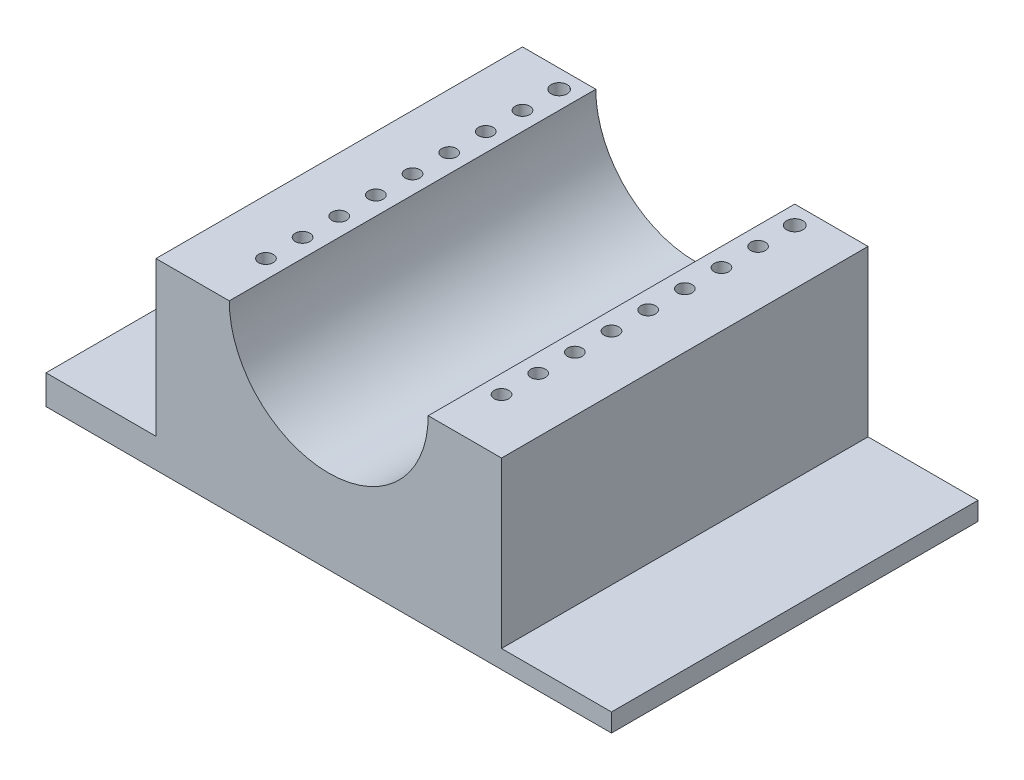
SolidWorks part; units mm, degrees
ref_plane "Front Plane" through (0, 0, 0) normal (0, 0, 1) x (1, 0, 0)
ref_plane "Top Plane" through (0, 0, 0) normal (0, 1, 0) x (1, 0, 0)
ref_plane "Right Plane" through (0, 0, 0) normal (1, 0, 0) x (0, 0, -1)
sketch "Sketch1" plane through (0, 0, 0) normal (0, 0, 1) x (1, 0, 0)
  line L0 (-57.1674, 32.8049) -> (-57.1674, -17.1951)
  line L1 (37.1126, -17.1951) -> (-57.1674, -17.1951)
  line L2 (37.1126, -17.1951) -> (37.1126, 32.8049)
  line L5 (-57.1674, 32.8049) -> (-37.1674, 32.8049)
  line L6 (37.1126, 32.8049) -> (17.1126, 32.8049)
  arc A0 (17.1126, 32.8049) -> (-37.1674, 32.8049) centre (-10.0274, 32.8049) cw
  point P0 (-10.0274, 32.8049)
extrude "Boss-Extrude1" add sketch "Sketch1" along normal blind 100
sketch "Sketch2" plane through (0, 32.8049, 0) normal (0, 1, 0) x (1, 0, 0)
  line L0 (-37.1674, -100) -> (-37.1674, 0) construction
  line L1 (-37.1674, 0) -> (-57.1674, 0) construction
  line L4 (-10.0274, -100) -> (-10.0274, 0)
  line L5 (17.1126, 0) -> (-37.1674, 0) construction
  line L6 (-37.1674, -100) -> (17.1126, -100) construction
  line L7 (-47.1674, 0) -> (-47.1674, -100)
  line L8 (-37.1674, -100) -> (-57.1674, -100) construction
  circle A0 centre (-42.1674, -5) radius 2.2
  circle A1 centre (-42.1674, -15) radius 2
  circle A2 centre (-42.1674, -25) radius 2
  circle A3 centre (-42.1674, -35) radius 2
  circle A4 centre (-42.1674, -45) radius 2
  circle A5 centre (-42.1674, -55) radius 2
  circle A6 centre (-42.1674, -65) radius 2
  circle A7 centre (-42.1674, -75) radius 2
  circle A8 centre (-42.1674, -85) radius 2
  circle A11 centre (22.1126, -85) radius 2
  circle A12 centre (22.1126, -75) radius 2
  circle A13 centre (22.1126, -65) radius 2
  circle A14 centre (22.1126, -55) radius 2
  circle A15 centre (22.1126, -45) radius 2
  circle A16 centre (22.1126, -35) radius 2
  circle A17 centre (22.1126, -25) radius 2
  circle A18 centre (22.1126, -15) radius 2
  circle A19 centre (22.1126, -5) radius 2.2
  point P28 (-10.0274, 0)
  point P31 (-10.0274, -50)
  point P35 (-47.1674, -50)
  point P36 (-10.0274, -100)
  point P59 (-47.1674, -100)
  point P61 (-47.1674, 0)
  dimension "D1" = 5
  dimension "D2" = 5
extrude "Cut-Extrude2" cut sketch "Sketch2" against normal blind 6 contours A11 | A8 | A7 | A6 | A16 | A13 | A5 | A4 | A3 | A0 | A19 | A18 | A17 | A15 | A14 | A12 | A1 | A2 region at (-42.1674, 32.8049, 65) region at (-42.1674, 32.8049, 75) region at (-42.1674, 32.8049, 85) region at (22.1126, 32.8049, 85) region at (22.1126, 32.8049, 65) region at (22.1126, 32.8049, 35)
sketch "Sketch3" plane through (-57.1674, 0, 0) normal (-1, 0, 0) x (0, 0, 1)
  line L8 (100, -17.1951) -> (0, -17.1951) construction
  line L9 (0, -17.1951) -> (100, -17.1951)
  line L10 (0, -17.1951) -> (0, -9.1951)
  line L11 (0, -9.1951) -> (100, -9.1951)
  line L12 (100, -17.1951) -> (100, -9.1951)
  line L13 (0, 32.8049) -> (0, -17.1951) construction
  line L14 (100, 32.8049) -> (100, -17.1951) construction
extrude "Boss-Extrude2" add sketch "Sketch3" along normal blind 30
sketch "Sketch4" plane through (37.1126, 0, 0) normal (1, 0, 0) x (0, 0, -1)
  line L0 (0, -17.1951) -> (0, 32.8049) construction
  line L1 (-100, -17.1951) -> (0, -17.1951)
  line L2 (-100, -17.1951) -> (-100, -12.1951)
  line L3 (-100, -12.1951) -> (0, -12.1951)
  line L4 (0, -17.1951) -> (0, -12.1951)
  line L5 (-100, -17.1951) -> (-100, 32.8049) construction
  line L7 (-100, -17.1951) -> (0, -17.1951) construction
extrude "Boss-Extrude3" add sketch "Sketch4" along normal blind 30
